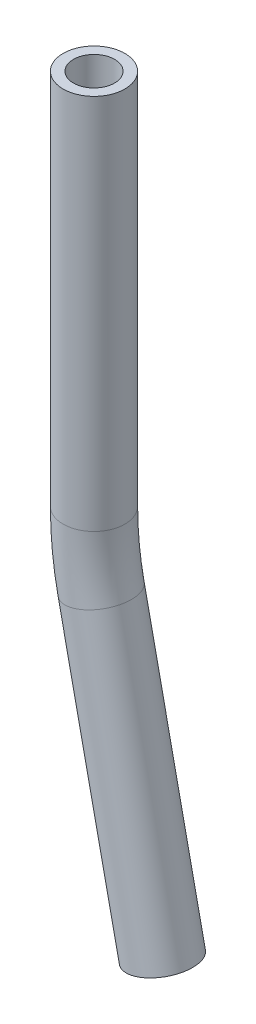
SolidWorks part; units mm, degrees
material "Silicon Rubber"
ref_plane "Front Plane" through (0, 0, 0) normal (0, 0, 1) x (1, 0, 0)
ref_plane "Top Plane" through (0, 0, 0) normal (0, 1, 0) x (1, 0, 0)
ref_plane "Right Plane" through (0, 0, 0) normal (1, 0, 0) x (0, 0, -1)
sketch "Sketch1" plane through (0, 0, 0) normal (0, 1, 0) x (1, 0, 0)
  circle A0 centre (0, 0) radius 4.7625
  circle A1 centre (0, 0) radius 3.175
  dimension "D1" = 9.525
  dimension "D2" = 6.35
sketch "Sketch2" plane through (0, 0, 0) normal (0, 0, 1) x (1, 0, 0)
  line L0 (0, 0) -> (0, -58.1607)
  line L1 (1.1101, -68.7226) -> (10.5619, -113.1899)
  arc A0 (0, -58.1607) -> (1.1101, -68.7226) centre (50.8, -58.1607) ccw
  point P6 (0, -63.5)
  dimension "D4" = 50.8
  dimension "D1" = 63.5
  dimension "D2" = 50.8
  dimension "D3" = 168
sweep "Sweep1" add profiles "Sketch1" path "Sketch2"
